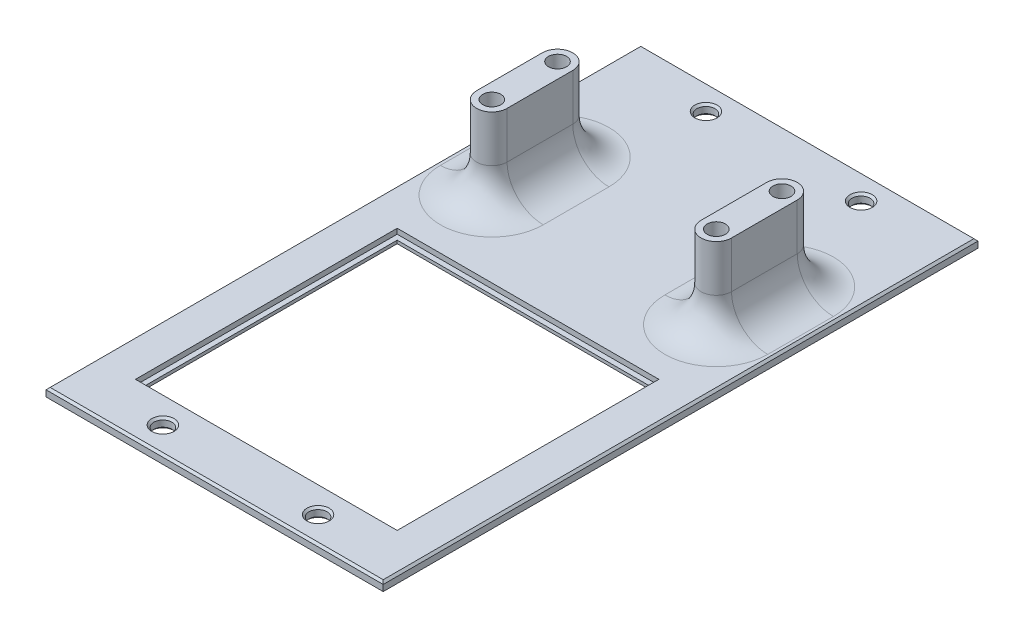
SolidWorks part; units mm, degrees
ref_plane "Front Plane" through (0, 0, 0) normal (0, 0, 1) x (1, 0, 0)
ref_plane "Top Plane" through (0, 0, 0) normal (0, 1, 0) x (1, 0, 0)
ref_plane "Right Plane" through (0, 0, 0) normal (1, 0, 0) x (0, 0, -1)
sketch "Sketch1" plane through (0, 0, 0) normal (0, 1, 0) x (1, 0, 0)
  line L0 (-24.3, 2.1) -> (-24.3, -46.5)
  line L1 (32.6, -57.5) -> (-32.6, -57.5)
  line L2 (32.6, -57.5) -> (32.6, 57.5)
  line L3 (32.6, 57.5) -> (-32.6, 57.5)
  line L4 (-32.6, -57.5) -> (-32.6, 57.5)
  line L5 (32.6, -57.5) -> (-32.6, 57.5) construction
  line L6 (32.6, 57.5) -> (-32.6, -57.5) construction
  line L11 (-25.3, 3.1) -> (25.3, 3.1) construction
  line L12 (0, -57.5) -> (0, -47.5) construction
  line L13 (0, 57.5) -> (0, 47.5) construction
  line L14 (-15, 52.5) -> (15, 52.5) construction
  line L15 (-15, -52.5) -> (15, -52.5) construction
  line L16 (-25.3, 3.1) -> (-25.3, -47.5) construction
  line L17 (-25.3, -47.5) -> (25.3, -47.5) construction
  line L18 (25.3, 3.1) -> (25.3, -47.5) construction
  line L19 (-24.3, -46.5) -> (24.3, -46.5)
  line L20 (24.3, 2.1) -> (24.3, -46.5)
  line L21 (-24.3, 2.1) -> (24.3, 2.1)
  circle A0 centre (-15, 52.5) radius 1.75
  circle A1 centre (15, 52.5) radius 1.75
  circle A2 centre (15, -52.5) radius 1.75
  circle A3 centre (-15, -52.5) radius 1.75
  point P0 (0, 0)
  point P11 (0, 0)
  point P20 (0, -52.5)
  point P21 (0, 52.5)
  dimension "D7" = 3.5
  dimension "D1" = 65.2
  dimension "D2" = 10
  dimension "D3" = 50.6
  dimension "D4" = 115
  dimension "D5" = 1
  dimension "D6" = 30
extrude "Boss-Extrude1" add sketch "Sketch1" along normal blind 1
sketch "Sketch3" plane through (0, 1, 0) normal (0, 1, 0) x (1, 0, 0)
  line L0 (-25.3, -47.5) -> (25.3, -47.5) construction
  line L1 (25.3, 3.1) -> (25.3, -47.5) construction
  line L2 (-25.3, 3.1) -> (25.3, 3.1) construction
  line L3 (-25.3, 3.1) -> (-25.3, -47.5) construction
  line L4 (-32.6, 57.5) -> (-32.6, -57.5)
  line L5 (-32.6, -57.5) -> (32.6, -57.5)
  line L6 (32.6, -57.5) -> (32.6, 57.5)
  line L7 (32.6, 57.5) -> (-32.6, 57.5)
  line L8 (-32.6, 57.5) -> (-32.6, -57.5)
  line L9 (-32.6, -57.5) -> (32.6, -57.5)
  line L10 (32.6, -57.5) -> (32.6, 57.5)
  line L11 (32.6, 57.5) -> (-32.6, 57.5)
  line L12 (-25.3, -47.5) -> (25.3, -47.5)
  line L13 (25.3, 3.1) -> (25.3, -47.5)
  line L14 (-25.3, 3.1) -> (25.3, 3.1)
  line L15 (-25.3, 3.1) -> (-25.3, -47.5)
  circle A0 centre (-15, -52.5) radius 1.75 construction
  circle A1 centre (15, -52.5) radius 1.75 construction
  circle A2 centre (15, 52.5) radius 1.75 construction
  circle A3 centre (-15, 52.5) radius 1.75 construction
  circle A4 centre (-15, -52.5) radius 1.75
  circle A5 centre (15, -52.5) radius 1.75
  circle A6 centre (15, 52.5) radius 1.75
  circle A7 centre (-15, 52.5) radius 1.75
  dimension "D1" = 0
extrude "Boss-Extrude2" add sketch "Sketch3" along normal blind 1
sketch "Sketch4" plane through (0, 2, 0) normal (0, 1, 0) x (1, 0, 0)
  line L0 (-21.7, 30.5) -> (-21.7, 17.8) construction
  line L1 (-18.75, 30.5) -> (-18.75, 17.8)
  line L2 (-24.65, 30.5) -> (-24.65, 17.8)
  line L3 (21.7, 30.5) -> (21.7, 17.8) construction
  line L4 (24.65, 30.5) -> (24.65, 17.8)
  line L5 (18.75, 30.5) -> (18.75, 17.8)
  line L6 (-21.7, 24.15) -> (21.7, 24.15) construction
  line L7 (0, 57.5) -> (0, 24.15) construction
  line L8 (32.6, 57.5) -> (-32.6, 57.5) construction
  arc A0 (-18.75, 30.5) -> (-24.65, 30.5) centre (-21.7, 30.5) ccw
  arc A1 (-24.65, 17.8) -> (-18.75, 17.8) centre (-21.7, 17.8) ccw
  arc A2 (24.65, 30.5) -> (18.75, 30.5) centre (21.7, 30.5) ccw
  arc A3 (18.75, 17.8) -> (24.65, 17.8) centre (21.7, 17.8) ccw
  circle A4 centre (15, 52.5) radius 1.75 construction
  circle A5 centre (-21.7, 30.5) radius 1.75
  circle A6 centre (-21.7, 17.8) radius 1.75
  circle A7 centre (21.7, 17.8) radius 1.75
  circle A8 centre (21.7, 30.5) radius 1.75
  point P2 (-21.7, 24.15)
  point P7 (21.7, 24.15)
  dimension "D4" = 3.5
  dimension "D5" = 1.2
  dimension "D1" = 12.7
  dimension "D2" = 43.4
  dimension "D3" = 22
extrude "Boss-Extrude3" add sketch "Sketch4" along normal blind 16
fillet "Fillet1" radius 7 8 edges at (18.75, 2, -24.15) (21.7, 2, -33.45) (24.65, 2, -24.15) (-24.65, 2, -24.15) (-21.7, 2, -33.45) (-18.75, 2, -24.15) (21.7, 2, -14.85) (-21.7, 2, -14.85)
sketch "Sketch5" plane through (0, 18, 0) normal (0, 1, 0) x (1, 0, 0)
  circle A0 centre (21.7, 30.5) radius 1.75 construction
  circle A1 centre (21.7, 17.8) radius 1.75 construction
  circle A2 centre (-21.7, 17.8) radius 1.75 construction
  circle A3 centre (-21.7, 30.5) radius 1.75 construction
  circle A4 centre (21.7, 30.5) radius 1.75
  circle A5 centre (21.7, 17.8) radius 1.75
  circle A6 centre (-21.7, 17.8) radius 1.75
  circle A7 centre (-21.7, 30.5) radius 1.75
extrude "Cut-Extrude1" cut sketch "Sketch5" against normal up to surface (18 mm away) up to face at (0, 0, 0)
sketch "Sketch6" plane through (0, 0, 0) normal (0, -1, 0) x (1, 0, 0)
  line L1 (-18.95, -16.2123) -> (-21.7, -14.6246)
  line L2 (-21.7, -14.6246) -> (-24.45, -16.2123)
  line L3 (-24.45, -16.2123) -> (-24.45, -19.3877)
  line L4 (-24.45, -19.3877) -> (-21.7, -20.9754)
  line L5 (-21.7, -20.9754) -> (-18.95, -19.3877)
  line L6 (-18.95, -19.3877) -> (-18.95, -16.2123)
  line L7 (-18.95, -28.9123) -> (-21.7, -27.3246)
  line L8 (-21.7, -27.3246) -> (-24.45, -28.9123)
  line L9 (-24.45, -28.9123) -> (-24.45, -32.0877)
  line L10 (-24.45, -32.0877) -> (-21.7, -33.6754)
  line L11 (-21.7, -33.6754) -> (-18.95, -32.0877)
  line L12 (-18.95, -32.0877) -> (-18.95, -28.9123)
  line L13 (18.95, -28.9123) -> (18.95, -32.0877)
  line L14 (18.95, -32.0877) -> (21.7, -33.6754)
  line L15 (21.7, -33.6754) -> (24.45, -32.0877)
  line L16 (24.45, -32.0877) -> (24.45, -28.9123)
  line L17 (24.45, -28.9123) -> (21.7, -27.3246)
  line L18 (21.7, -27.3246) -> (18.95, -28.9123)
  line L19 (18.95, -16.2123) -> (18.95, -19.3877)
  line L20 (18.95, -19.3877) -> (21.7, -20.9754)
  line L21 (21.7, -20.9754) -> (24.45, -19.3877)
  line L22 (24.45, -19.3877) -> (24.45, -16.2123)
  line L23 (24.45, -16.2123) -> (21.7, -14.6246)
  line L24 (21.7, -14.6246) -> (18.95, -16.2123)
  circle A0 centre (-21.7, -17.8) radius 2.75 construction
  circle A1 centre (-21.7, -30.5) radius 2.75 construction
  circle A2 centre (21.7, -30.5) radius 2.75 construction
  circle A3 centre (21.7, -17.8) radius 2.75 construction
  dimension "D1" = 5.5
extrude "Cut-Extrude2" cut sketch "Sketch6" against normal blind 3
chamfer "Chamfer1" distance 1.6 angle 45 4 edges at (21.7, 3, -32.25) (21.7, 3, -19.55) (-21.7, 3, -19.55) (-21.7, 3, -32.25)
chamfer "Chamfer2" distance 0.4 angle 45 44 edges at (-15, 0, 54.25) (15, 0, 54.25) (15, 0, -50.75) (-15, 0, -50.75) (24.3, 0, 22.2) (0, 0, 46.5) (-24.3, 0, 22.2) (0, 0, -2.1) (0, 0, 57.5) (32.6, 0, 0) (0, 0, -57.5) (-32.6, 0, 0) (-23.075, 0, -15.4184) (-24.45, 0, -17.8) (-23.075, 0, -20.1816) (-20.325, 0, -20.1816) (-18.95, 0, -17.8) (-20.325, 0, -15.4184) (-23.075, 0, -28.1184) (-24.45, 0, -30.5) (-23.075, 0, -32.8816) (-20.325, 0, -32.8816) (-18.95, 0, -30.5) (-20.325, 0, -28.1184) (20.325, 0, -32.8816) (23.075, 0, -32.8816) (24.45, 0, -30.5) (23.075, 0, -28.1184) (20.325, 0, -28.1184) (18.95, 0, -30.5) (20.325, 0, -20.1816) (23.075, 0, -20.1816) (24.45, 0, -17.8) (23.075, 0, -15.4184) (20.325, 0, -15.4184) (18.95, 0, -17.8) (15, 2, 54.25) (-15, 2, 54.25) (-15, 2, -50.75) (15, 2, -50.75) (0, 2, -57.5) (32.6, 2, 0) (0, 2, 57.5) (-32.6, 2, 0)
